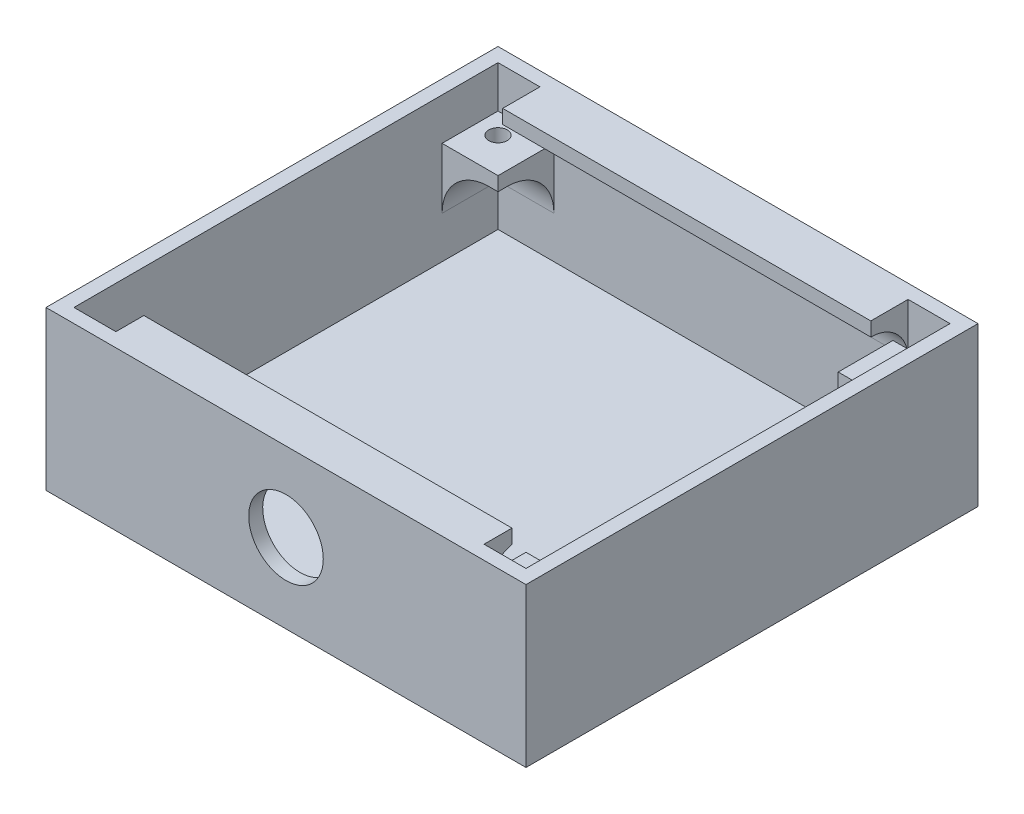
SolidWorks part; units mm, degrees
ref_plane "Front Plane" through (0, 0, 0) normal (0, 0, 1) x (1, 0, 0)
ref_plane "Top Plane" through (0, 0, 0) normal (0, 1, 0) x (1, 0, 0)
ref_plane "Right Plane" through (0, 0, 0) normal (1, 0, 0) x (0, 0, -1)
sketch "Sketch1" plane through (0, 0, 0) normal (0, 1, 0) x (1, 0, 0)
  line L0 (0, 0) -> (48.5, 0)
  line L1 (48.5, 0) -> (48.5, 45.5)
  line L2 (48.5, 45.5) -> (0, 45.5)
  line L3 (0, 45.5) -> (0, 0)
  line L4 (4.5, 0) -> (4.5, 4.5)
  line L5 (4.5, 4.5) -> (0, 4.5)
  line L6 (4.5, 4.5) -> (0, 0) construction
  line L7 (0, 41) -> (4.5, 41)
  line L8 (4.5, 41) -> (4.5, 45.5)
  line L9 (44, 45.5) -> (44, 41)
  line L10 (44, 41) -> (48.5, 41)
  line L11 (44, 0) -> (44, 4.5)
  line L12 (44, 4.5) -> (48.5, 4.5)
  line L13 (44, 4.5) -> (48.5, 0) construction
  line L14 (44, 41) -> (48.5, 45.5) construction
  line L15 (4.5, 41) -> (0, 45.5) construction
  line L16 (-1.5, 47) -> (-1.5, -1.5)
  line L17 (4.5, 41.5) -> (44, 41.5)
  line L18 (-1.5, -1.5) -> (50, -1.5)
  line L19 (50, -1.5) -> (50, 47)
  line L20 (50, 47) -> (-1.5, 47)
  line L22 (6, 0) -> (6, 6)
  line L23 (6, 6) -> (0, 6)
  line L24 (0, 39.5) -> (6, 39.5)
  line L25 (6, 39.5) -> (6, 45.5)
  line L26 (42.5, 45.5) -> (42.5, 39.5)
  line L27 (42.5, 39.5) -> (48.5, 39.5)
  line L28 (48.5, 6) -> (42.5, 6)
  line L29 (42.5, 6) -> (42.5, 0)
  line L31 (4.5, 3) -> (44, 3)
  circle A0 centre (2.25, 2.25) radius 1
  circle A1 centre (46.25, 2.25) radius 1
  circle A2 centre (46.25, 43.25) radius 1
  circle A3 centre (2.25, 43.25) radius 1
  dimension "D4" = 2
  dimension "D1" = 48.5
  dimension "D2" = 45.5
  dimension "D3" = 4.5
  dimension "D6" = 6
  dimension "D8" = 3
  dimension "D5" = 4
  dimension "D14" = 1.5
extrude "base" add sketch "Sketch1" along normal blind 1.5 contours L18 L19 L20 L16
extrude "walls" add sketch "Sketch1<6>" along normal blind 17 contours L19 L20 L16 L18 L3 L2 L1 L0 region at (24.25, 0, -46.2926)
sketch "Sketch1<6>" plane through (0, 0, 0) normal (0, 1, 0) x (1, 0, 0) same geometry as "Sketch1"
extrude "screws" add sketch "Sketch1<7>" along normal blind 1.5 from offset 11 contours L12 L11 L0 L1 A1 | L29 L31 L11 L12 L1 L28 | L31 L29 L0 L11 | L26 L27 L1 L10 L9 L17 | L9 L10 L1 L2 A2 | L2 L26 L17 L9 | L24 L25 L17 L8 L7 L3 | L7 L8 L2 L3 A3 | L17 L25 L2 L8 | L4 L5 L3 L0 A0 | L4 L31 L22 L23 L3 L5 | L31 L4 L0 L22 region at (0.0636, 0, -2.25) region at (5.25, 0, -1.5) region at (3.45, 0, -4.95) region at (43.25, 0, -1.5) region at (3.1731, 0, -40.3269) region at (44.0636, 0, -1.5) region at (45.05, 0, -4.95) region at (0.0636, 0, -43.25) region at (5.25, 0, -43.5) region at (43.25, 0, -43.5) region at (45.3269, 0, -40.3269) region at (44.0636, 0, -43.5)
sketch "Sketch1<7>" plane through (0, 0, 0) normal (0, 1, 0) x (1, 0, 0) same geometry as "Sketch1"
extrude "top" add sketch "Sketch1<8>" along normal blind 1.5 from offset 15.5 contours L26 L2 L25 L17 | L17 L25 L2 L8 | L2 L26 L17 L9 | L31 L4 L0 L22 | L31 L22 L0 L29 | L31 L29 L0 L11 region at (5.25, 0, -1.5) region at (24.25, 0, -1.5) region at (43.25, 0, -1.5) region at (24.25, 0, -43.5) region at (5.25, 0, -43.5) region at (43.25, 0, -43.5)
sketch "Sketch1<8>" plane through (0, 0, 0) normal (0, 1, 0) x (1, 0, 0) same geometry as "Sketch1"
fillet "Fillet1" radius 5 8 edges at (3, 11, 0) (0, 11, -3) (0, 11, -42.5) (3, 11, -45.5) (45.5, 11, -45.5) (48.5, 11, -42.5) (48.5, 11, -3) (45.5, 11, 0)
fillet "Fillet3" radius 4 2 edges at (24.25, 15.5, 0) (24.25, 15.5, -45.5)
sketch "Sketch2" plane through (0, 0, 1.5) normal (0, 0, 1) x (1, 0, 0)
  line L0 (50, 17) -> (-1.5, 0) construction
  line L1 (-1.5, 17) -> (50, 0) construction
  circle A0 centre (24.25, 8.5) radius 4
  dimension "D1" = 8
extrude "Cut-Extrude1" cut sketch "Sketch2" against normal blind 1.5 contours A0
